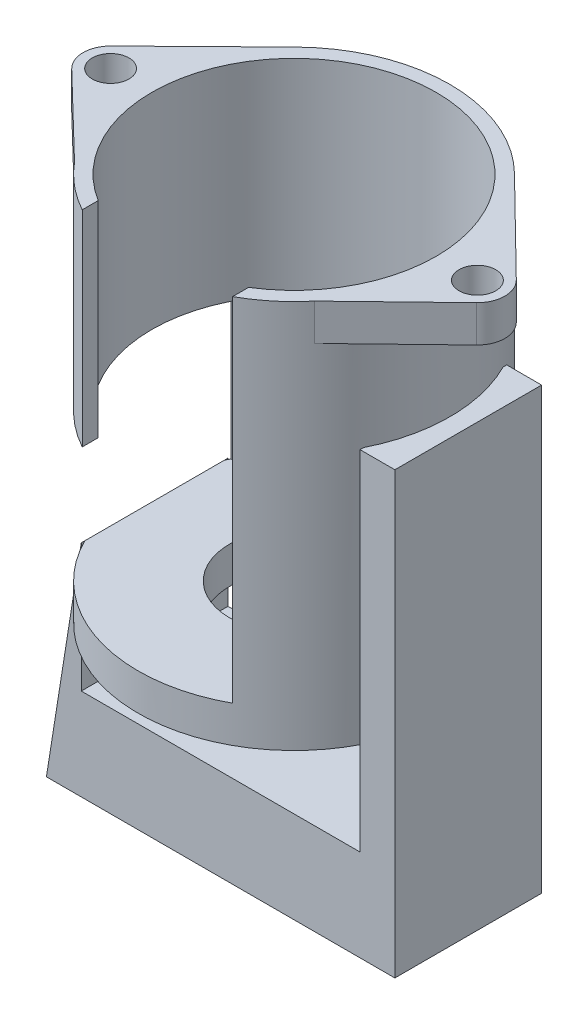
SolidWorks part; units mm, degrees
ref_plane "前视基准面" through (0, 0, 0) normal (0, 0, 1) x (1, 0, 0)
ref_plane "上视基准面" through (0, 0, 0) normal (0, 1, 0) x (1, 0, 0)
ref_plane "右视基准面" through (0, 0, 0) normal (1, 0, 0) x (0, 0, -1)
sketch "草图2" plane through (0, 0, 0) normal (0, 1, 0) x (1, 0, 0)
  line L0 (-9.5, 0) -> (9.5, 0) construction
  line L1 (-9.5, 4) -> (9.5, 4)
  line L2 (-9.5, 4) -> (-9.5, -4)
  line L3 (-9.5, -4) -> (9.5, -4)
  line L4 (9.5, 4) -> (9.5, -4)
  line L5 (-9.5, 4) -> (9.5, -4) construction
  line L6 (-9.5, -4) -> (9.5, 4) construction
  point P0 (0, 0)
  dimension "D1" = 19
  dimension "D2" = 4
extrude "凸台-拉伸1" add sketch "草图2" against normal blind 9
sketch "草图4" plane through (0, 0, 0) normal (0, 1, 0) x (1, 0, 0)
  circle A0 centre (0, 0) radius 8.5
  dimension "D1" = 17
extrude "凸台-拉伸2" add sketch "草图4" along normal blind 22.2
sketch "草图5" plane through (0, 0, 0) normal (0, 1, 0) x (1, 0, 0)
  circle A0 centre (0, 0) radius 7.75
extrude "切除-拉伸5" cut sketch "草图5<2>" along normal up to next
sketch "草图5<2>" plane through (0, 0, 0) normal (0, 1, 0) x (1, 0, 0) same geometry as "草图5"
ref_plane "基准面1" through (0, 22.2, 0) normal (0, 1, 0) x (1, 0, 0)
sketch "草图9" plane through (0, 22.2, 0) normal (0, 1, 0) x (1, 0, 0)
  line L0 (-11.05, 1.0712) -> (-5.95, 6.0702)
  line L1 (-11.0421, -1.0789) -> (-6.5487, -5.4189)
  line L2 (0, 0) -> (0, 8.5) construction
  line L3 (11.0421, -1.0789) -> (6.5487, -5.4189)
  line L4 (11.05, 1.0712) -> (5.95, 6.0702)
  circle A0 centre (-10, 0) radius 1
  arc A1 (-6.5487, -5.4189) -> (6.5487, -5.4189) centre (0, 0) ccw
  arc A2 (-11.05, 1.0712) -> (-11.0421, -1.0789) centre (-10, 0) ccw
  arc A3 (11.05, 1.0712) -> (11.0421, -1.0789) centre (10, 0) cw
  circle A4 centre (10, 0) radius 1
  arc A5 (5.95, 6.0702) -> (-5.95, 6.0702) centre (0, 0) ccw
  dimension "D1" = 2
extrude "凸台-拉伸4" add sketch "草图9" against normal blind 2
extrude "切除-拉伸8" cut sketch "草图5" along normal through all
sketch "草图11" plane through (0, 0, 0) normal (0, 1, 0) x (1, 0, 0)
  line L0 (-6.638, -4) -> (6.638, -4) construction
  line L1 (-7.6, 4) -> (7.6, 4)
  line L2 (-7.6, 4) -> (-7.6, -4)
  line L3 (-7.6, -4) -> (7.6, -4)
  line L4 (7.6, 4) -> (7.6, -4)
  line L5 (-7.6, 4) -> (7.6, -4) construction
  line L6 (-7.6, -4) -> (7.6, 4) construction
  point P0 (0, 0)
extrude "切除-拉伸11" cut sketch "草图11" against normal blind 4
sketch "草图12" plane through (0, 0, 0) normal (0, 0, 1) x (1, 0, 0)
  line L0 (8.7702, 22.2) -> (-8.7702, 22.2) construction
  line L1 (-4.1, 22.2) -> (4.1, 22.2)
  line L2 (-4.1, 22.2) -> (-4.1, 0)
  line L3 (-4.1, 0) -> (4.1, 0)
  line L4 (4.1, 22.2) -> (4.1, 0)
  line L5 (-7.6, 0) -> (7.6, 0) construction
extrude "切除-拉伸12" cut sketch "草图12" along normal through all
sketch "草图13" plane through (0, 0, 0) normal (1, 0, 0) x (0, 0, -1)
  line L0 (-7.4458, 0) -> (-7.4458, 22.2) construction
  line L1 (-7.4458, 11) -> (4.0482, 11)
  line L2 (-7.4458, 11) -> (-7.4458, 3)
  line L3 (-7.4458, 3) -> (4.0482, 3)
  line L4 (4.0482, 11) -> (4.0482, 3)
  line L5 (8.7702, 22.2) -> (-8.7702, 22.2) construction
  dimension "D1" = 19.2
  dimension "D2" = 8
extrude "切除-拉伸13" cut sketch "草图13" against normal through all
sketch "草图14" plane through (0, 0, 0) normal (0, 1, 0) x (1, 0, 0)
  line L5 (-7.6, 3.8066) -> (-7.6, 4)
  line L6 (-7.6, 4) -> (-9.5, 4)
  line L7 (-9.5, 4) -> (-9.5, -4)
  line L8 (-9.5, -4) -> (-7.6, -4)
  line L9 (-7.6, -4) -> (-7.6, -3.8066)
  line L10 (-7.6, 3.8066) -> (-7.6, 4)
  line L11 (-7.6, 4) -> (-9.5, 4)
  line L12 (-9.5, 4) -> (-9.5, -4)
  line L13 (-9.5, -4) -> (-7.6, -4)
  line L14 (-7.6, -4) -> (-7.6, -3.8066)
  arc A1 (-7.6, 3.8066) -> (-7.6, -3.8066) centre (0, 0) ccw
  arc A2 (-7.6, 3.8066) -> (-7.6, -3.8066) centre (0, 0) ccw
  dimension "D1" = 0
extrude "凸台-拉伸6" add sketch "草图14" along normal blind 3
sketch "草图15" plane through (0, 0, 0) normal (0, 1, 0) x (1, 0, 0)
  line L5 (7.6, -3.8066) -> (7.6, -4)
  line L6 (7.6, -4) -> (9.5, -4)
  line L7 (9.5, -4) -> (9.5, 4)
  line L8 (9.5, 4) -> (7.6, 4)
  line L9 (7.6, 4) -> (7.6, 3.8066)
  line L10 (7.6, -3.8066) -> (7.6, -4)
  line L11 (7.6, -4) -> (9.5, -4)
  line L12 (9.5, -4) -> (9.5, 4)
  line L13 (9.5, 4) -> (7.6, 4)
  line L14 (7.6, 4) -> (7.6, 3.8066)
  arc A1 (7.6, -3.8066) -> (7.6, 3.8066) centre (0, 0) ccw
  arc A2 (7.6, -3.8066) -> (7.6, 3.8066) centre (0, 0) ccw
  dimension "D1" = 0
extrude "凸台-拉伸7" add sketch "草图15" along normal blind 15
sketch "草图16" plane through (0, -4, 0) normal (0, 1, 0) x (1, 0, 0)
  line L0 (0, 4) -> (0, -4) construction
  line L1 (7.6, 4) -> (-7.6, 4) construction
  line L2 (-7.6, -4) -> (7.6, -4) construction
  circle A0 centre (-6, 0) radius 1
  circle A1 centre (6, 0) radius 1
extrude "切除-拉伸14" cut sketch "草图16" against normal through all
ref_plane "基准面13" through (0, 3, 0) normal (0, 1, 0) x (1, 0, 0)
sketch "草图17" plane through (0, 3, 0) normal (0, 1, 0) x (1, 0, 0)
  circle A0 centre (0, 0) radius 8.5
  circle A1 centre (0, 0) radius 3.5
  dimension "D1" = 7
extrude "凸台-拉伸8" add sketch "草图17" against normal blind 2
sketch "草图18" plane through (0, 0, 0) normal (0, 0, 1) x (1, 0, 0)
  line L0 (-7.6, 3) -> (-9.5, -9)
  line L1 (-9.5, -9) -> (-9.5, 3)
  line L2 (-9.5, 3) -> (-7.6, 3)
extrude "切除-拉伸15" cut sketch "草图18" against normal through all both and the other way through all
sketch "草图19" plane through (0, 0, 0) normal (0, 1, 0) x (1, 0, 0)
  line L0 (-7.5, -4) -> (-7.5, 4)
  line L1 (-9.5, -4) -> (9.5, -4) construction
  arc A0 (-7.5, -4) -> (-7.5, 4) centre (0, 0) ccw
extrude "切除-拉伸17" cut sketch "草图19" along normal blind 1
